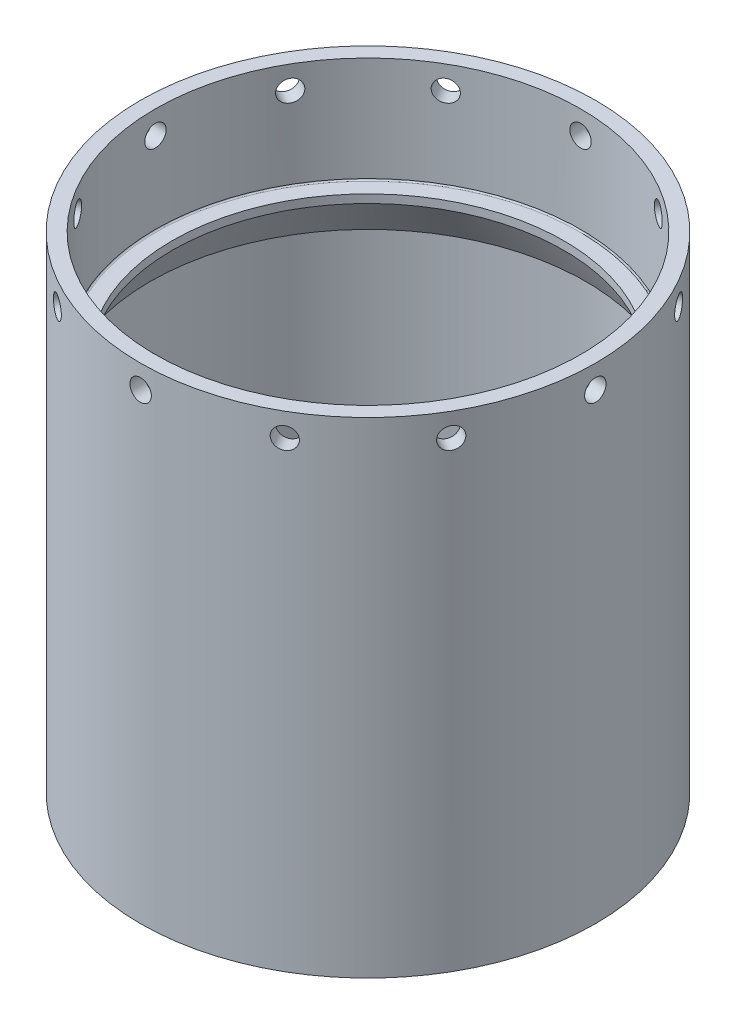
SolidWorks part; units mm, degrees
material "AISI 304"
ref_plane "Front Plane" through (0, 0, 0) normal (0, 0, 1) x (1, 0, 0)
ref_plane "Top Plane" through (0, 0, 0) normal (0, 1, 0) x (1, 0, 0)
ref_plane "Right Plane" through (0, 0, 0) normal (1, 0, 0) x (0, 0, -1)
sketch "Sketch2" plane through (0, 0, 0) normal (0, 0, 1) x (1, 0, 0)
  line L4 (0, 0) -> (0, -101.6) construction
  line L6 (59.69, 0) -> (64.8208, 0)
  line L7 (59.69, 0) -> (59.69, -2.54)
  line L8 (57.15, -115.6884) -> (69.342, -115.6884)
  line L9 (69.342, 32.2199) -> (69.342, -115.6884)
  line L12 (64.8208, 0) -> (64.8208, 32.2199)
  line L13 (64.8208, 32.2199) -> (69.342, 32.2199)
  line L14 (59.69, -2.54) -> (66.3575, -14.0884)
  line L15 (66.3575, -14.0884) -> (66.3575, -91.44)
  line L17 (59.69, -111.289) -> (59.69, -102.9884)
  line L18 (59.69, -102.9884) -> (66.3575, -91.44)
  line L19 (59.69, -111.289) -> (57.15, -115.6884)
  dimension "D5" = 32.2199
  dimension "D7" = 129.6416
  dimension "D2" = 119.38
  dimension "D3" = 4.5212
  dimension "D4" = 132.715
  dimension "D8" = 138.684
  dimension "D9" = 30
  dimension "D10" = 2.54
  dimension "D11" = 30
  dimension "D14" = 119.38
  dimension "D15" = 114.3
  dimension "D16" = 30
  dimension "D12" = 12.7
  dimension "D13" = 101.6
revolve "Revolve1" add sketch "Sketch2" angle 360 about L4
fillet "Fillet1" radius 0.4064 1 edges at (-64.8208, 0, 0)
ref_plane "Plane1" through (0, 0, 69.342) normal (0, 0, 1) x (1, 0, 0)
sketch "Sketch3" plane through (0, 0, 69.342) normal (0, 0, 1) x (1, 0, 0)
  line L1 (64.4144, 0) -> (-64.4144, 0) construction
  point P0 (0, 25.146)
  point P5 (0, 25.7284)
  dimension "D1" = 25.146
hole_wizard "F (0.257) Injector Hole" positions "Sketch3" profile "Sketch4" hole size "F" standard "ANSI Inch" end condition up to next
sketch "Sketch4" plane through (0, 25.146, 69.342) normal (1, 0, 0) x (0, -1, 0)
  line L0 (0, 0) -> (0, 4.5212)
  line L1 (0, 4.5212) -> (3.2639, 4.5212)
  line L2 (3.2639, 4.5212) -> (3.2639, 0)
  line L5 (3.2639, 0) -> (0, 0)
  line L11 (0, -6.35) -> (0, 107.95) construction
  dimension "Thru Hole Dia." = 6.5278
  dimension "Thru Hole Depth" = 4.5212
sketch "Sketch5" plane through (0, -115.6884, 0) normal (0, -1, 0) x (1, 0, 0)
  line L0 (0, 64.516) -> (-61.3584, 19.9365) construction
  line L1 (-61.3584, 19.9365) -> (-37.9216, -52.1945) construction
  line L2 (-37.9216, -52.1945) -> (37.9216, -52.1945) construction
  line L3 (37.9216, -52.1945) -> (61.3584, 19.9365) construction
  line L4 (61.3584, 19.9365) -> (0, 64.516) construction
  circle A1 centre (0, 0) radius 64.516 construction
  point P0 (0, 64.516)
  point P8 (61.3584, 19.9365)
  point P10 (37.9216, -52.1945)
  point P12 (-37.9216, -52.1945)
  point P14 (-61.3584, 19.9365)
  dimension "D1" = 129.032
hole_wizard "1/4-20 Tapped Nozzle Hole" positions "Sketch5" profile "Sketch6" tap size "1/4-20" standard "ANSI Inch"
sketch "Sketch6" plane through (0, -115.6884, 64.516) normal (1, 0, 0) x (0, 0, -1)
  line L0 (0, 0) -> (0, 14.2338)
  line L1 (0, 14.2338) -> (2.5527, 12.7)
  line L2 (2.5527, 12.7) -> (2.5527, 6.985)
  line L3 (2.5527, 6.985) -> (3.175, 6.985)
  line L4 (3.175, 6.985) -> (3.175, 0)
  line L5 (3.175, 0) -> (0, 0)
  line L10 (0, 14.2338) -> (-2.5527, 12.7) construction
  line L11 (0, -6.35) -> (0, 107.95) construction
  dimension "Tap Drill Dia." = 5.1054
  dimension "Tap Drill Depth" = 12.7
  dimension "Thread Major Dia." = 6.35
  dimension "Thread Depth" = 6.985
  dimension "Drill Angle" = 118
pattern_circular "CirPattern1" count 12 over 360 about axis through (0, 0, 0) along (0, 1, 0) of "F (0.257) Injector Hole" reverse direction yes
equation "\"length\"= 4in"
equation "\"bearingThickness\"= 0.178in"
equation "\"chamberID\"=5.225"
equation "\"D3@Sketch2\"=\"bearingThickness\""
equation "\"D4@Sketch2\"=\"chamberID\""
equation "\"D13@Sketch2\"=\"length\""
